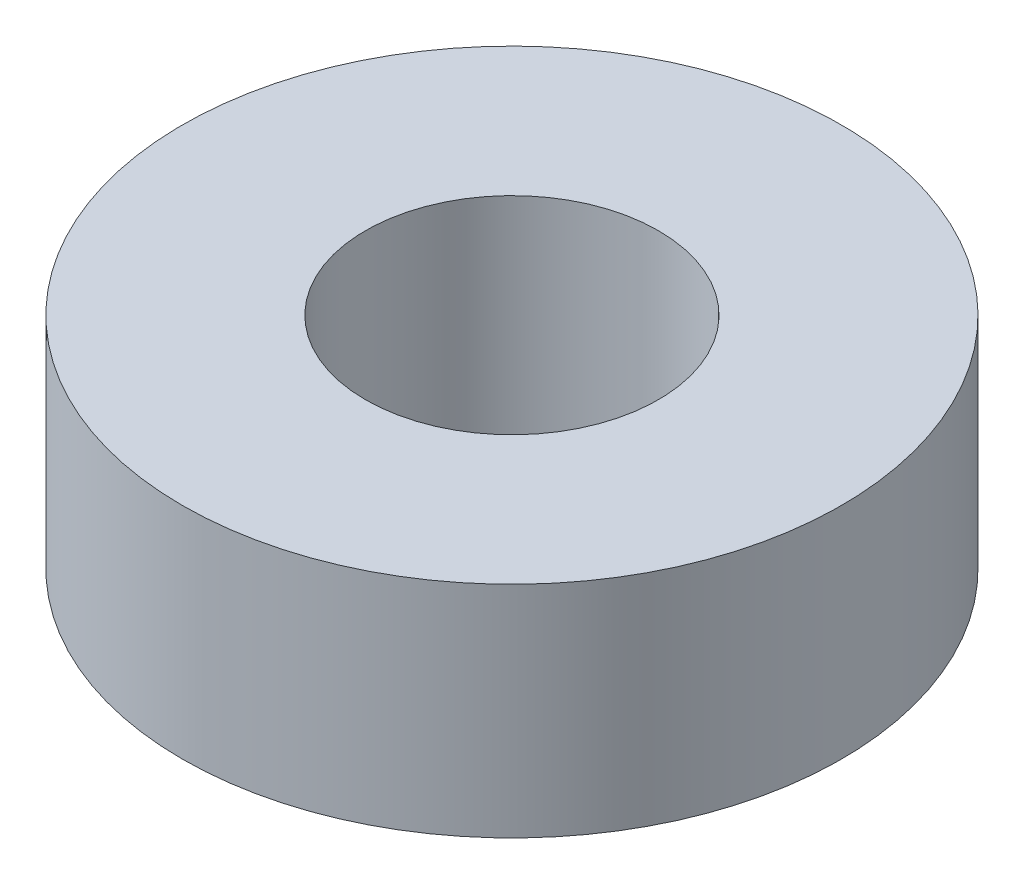
SolidWorks part; units mm, degrees
ref_plane "Front Plane" through (0, 0, 0) normal (0, 0, 1) x (1, 0, 0)
ref_plane "Top Plane" through (0, 0, 0) normal (0, 1, 0) x (1, 0, 0)
ref_plane "Right Plane" through (0, 0, 0) normal (1, 0, 0) x (0, 0, -1)
sketch "Sketch1" plane through (0, 0, 0) normal (0, 1, 0) x (1, 0, 0)
  circle A0 centre (0, 0) radius 22.5
  dimension "FLANGE_OD" = 45
extrude "Boss-Extrude1" add sketch "Sketch1" along normal blind 15
sketch "Sketch2" plane through (0, 0, 0) normal (0, 1, 0) x (1, 0, 0)
  circle A0 centre (0, 0) radius 10
  dimension "BORE_D" = 20
extrude "Cut-Extrude1" cut sketch "Sketch2" along normal through all
sketch "Sketch3" plane through (0, 15, 0) normal (0, 1, 0) x (1, 0, 0)
  circle A0 centre (0, 0) radius 7.7098 construction
  circle A1 centre (-7.7098, 0) radius 2.1941
  dimension "BOLT_D" = 4.3882
  dimension "BOLT_PCD" = 15.4196
extrude "Cut-Extrude2" cut sketch "Sketch3" against normal blind 9.5255 rebuild error yes
pattern_circular "CirPattern1" count 6 over 360 rebuild error yes
